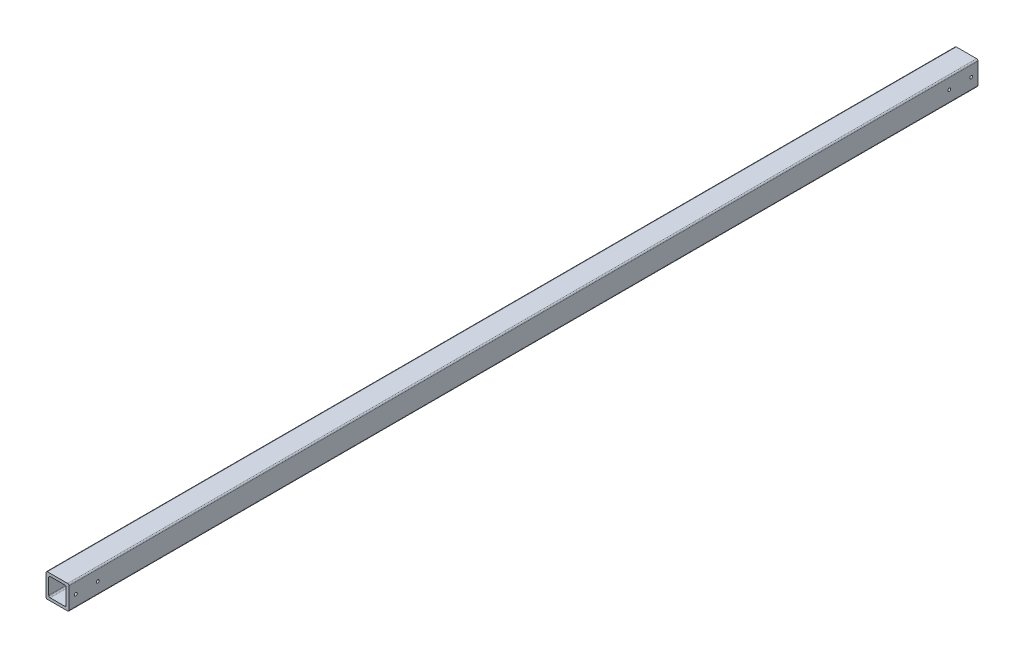
SolidWorks part; units mm, degrees
ref_plane "Front Plane" through (0, 0, 0) normal (0, 0, 1) x (1, 0, 0)
ref_plane "Top Plane" through (0, 0, 0) normal (0, 1, 0) x (1, 0, 0)
ref_plane "Right Plane" through (0, 0, 0) normal (1, 0, 0) x (0, 0, -1)
sketch "Main" plane through (0, 0, 0) normal (0, 1, 0) x (1, 0, 0)
  line L1 (-23.368, -844.55) -> (23.368, -844.55)
  line L2 (-23.368, -844.55) -> (-23.368, 844.55)
  line L3 (-23.368, 844.55) -> (23.368, 844.55)
  line L4 (23.368, -844.55) -> (23.368, 844.55)
  line L5 (-23.368, -844.55) -> (23.368, 844.55) construction
  line L6 (-23.368, 844.55) -> (23.368, -844.55) construction
  point P0 (0, 0)
  dimension "D1" = 1689.1
  dimension "D2" = 46.736
extrude "Extrude-Main" add sketch "Main" along normal blind 44.45
sketch "Main Cut" plane through (0, 0, 844.55) normal (0, 0, 1) x (1, 0, 0)
  line L0 (13.97, 5.08) -> (23.368, 5.08) construction
  line L5 (23.368, 44.45) -> (23.368, 0) construction
  line L7 (-23.368, 0) -> (23.368, 0) construction
  line L8 (-23.368, 44.45) -> (23.368, 44.45) construction
  line L9 (13.97, 5.08) -> (-18.288, 5.08)
  line L10 (13.97, 5.08) -> (13.97, 39.37)
  line L11 (13.97, 39.37) -> (-18.288, 39.37)
  line L12 (-18.288, 5.08) -> (-18.288, 39.37)
  line L13 (-23.368, 44.45) -> (-23.368, 0) construction
  dimension "D1" = 5.08
  dimension "D2" = 5.08
  dimension "D3" = 5.08
extrude "Cut-Main" cut sketch "Main Cut" against normal through all
sketch "Sketch1" plane through (0, 0, 844.55) normal (0, 0, 1) x (1, 0, 0)
  line L0 (-23.368, 44.45) -> (23.368, 44.45) construction
  line L1 (19.431, 44.45) -> (23.368, 44.45)
  line L2 (19.431, 44.45) -> (19.431, 0)
  line L3 (19.431, 0) -> (23.368, 0)
  line L4 (23.368, 44.45) -> (23.368, 0)
  dimension "D1" = 3.937
extrude "Cut-Extrude1" cut sketch "Sketch1" against normal through all
sketch "Sketch2" plane through (13.97, 0, 0) normal (-1, 0, 0) x (0, 0, 1)
  line L0 (844.55, 22.225) -> (-844.55, 22.225) construction
  line L1 (844.55, 5.08) -> (844.55, 39.37) construction
  line L2 (-844.55, 5.08) -> (-844.55, 39.37) construction
  line L3 (0, 44.45) -> (0, 0) construction
  line L4 (-844.55, 44.45) -> (844.55, 44.45) construction
  point P6 (-831.85, 22.225)
  point P7 (-791.21, 22.225)
  point P13 (791.21, 22.225)
  point P14 (831.85, 22.225)
  dimension "D1" = 12.7
  dimension "D2" = 53.34
hole_wizard "#4 (0.209) Diameter Hole2" positions "Sketch2" profile "Sketch5" hole size "#4" standard "ANSI Inch" end condition through all
sketch "Sketch5" plane through (13.97, 22.225, 831.85) normal (0, 1, 0) x (0, 0, 1)
  line L0 (0, 0) -> (0, 5.461)
  line L1 (0, 5.461) -> (2.6543, 5.461)
  line L2 (2.6543, 5.461) -> (2.6543, 0)
  line L5 (2.6543, 0) -> (0, 0)
  line L11 (0, -6.35) -> (0, 107.95) construction
  dimension "Thru Hole Dia." = 5.3086
  dimension "Thru Hole Depth" = 5.461
fillet "Fillet1" radius 2.54 8 edges at (-18.288, 39.37, 0) (13.97, 39.37, 0) (13.97, 5.08, 0) (-18.288, 5.08, 0) (19.431, 0, 0) (-23.368, 0, 0) (19.431, 44.45, 0) (-23.368, 44.45, 0)
